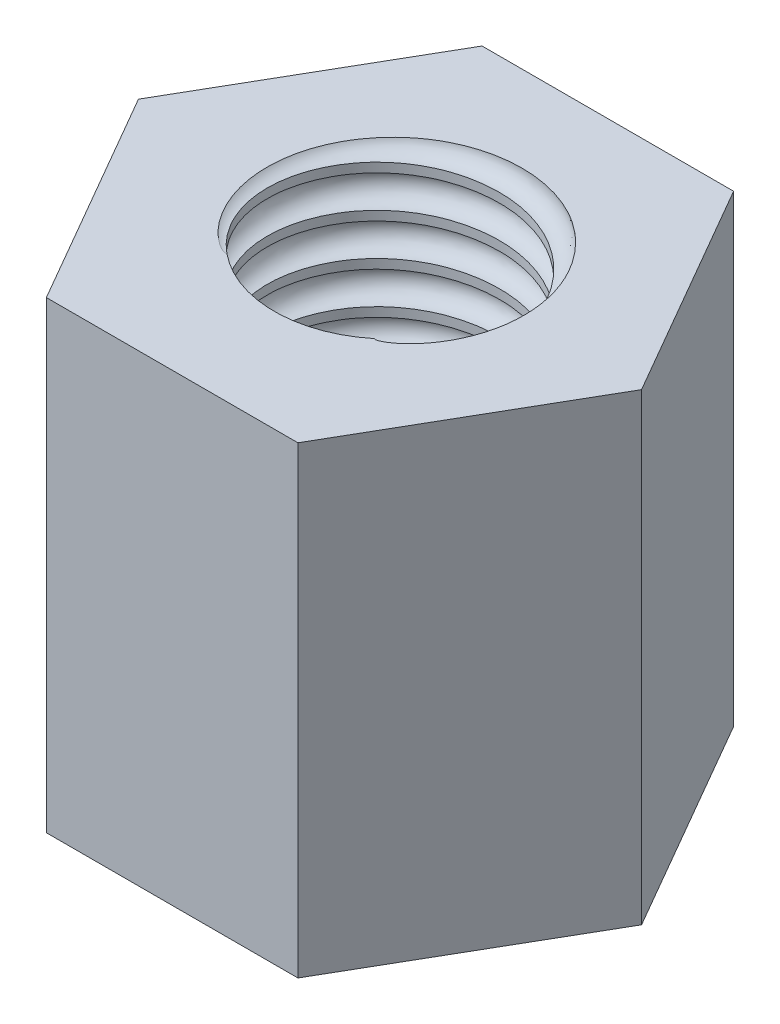
SolidWorks part; units mm, degrees
ref_plane "Front Plane" through (0, 0, 0) normal (0, 0, 1) x (1, 0, 0)
ref_plane "Top Plane" through (0, 0, 0) normal (0, 1, 0) x (1, 0, 0)
ref_plane "Right Plane" through (0, 0, 0) normal (1, 0, 0) x (0, 0, -1)
sketch "Sketch1" plane through (0, 0, 0) normal (0, 1, 0) x (1, 0, 0)
  line L1 (1.3568, -2.35) -> (2.7135, 0)
  line L2 (2.7135, 0) -> (1.3568, 2.35)
  line L3 (1.3568, 2.35) -> (-1.3568, 2.35)
  line L4 (-1.3568, 2.35) -> (-2.7135, 0)
  line L5 (-2.7135, 0) -> (-1.3568, -2.35)
  line L6 (-1.3568, -2.35) -> (1.3568, -2.35)
  circle A0 centre (0, 0) radius 2.35 construction
  point P1 (0, 2.35)
  dimension "D1" = 4.7
extrude "Boss-Extrude1" add sketch "Sketch1" along normal blind 5
sketch "Sketch2" plane through (0, 0, 0) normal (0, -1, 0) x (1, 0, 0)
  circle A0 centre (0, 0) radius 1.25
  dimension "D1" = 2.5
extrude "Boss-Extrude2" add sketch "Sketch2" along normal blind 6
sketch "Sketch4" plane through (0, -6, 0) normal (0, -1, 0) x (1, 0, 0)
  circle A0 centre (0, 0) radius 1.25 construction
  circle A1 centre (0, 0) radius 1.25
curve "Helix/Spiral1" pitch 0.45 height 5.9625 turns 13.25
sketch "Sketch5" plane through (0, 0, 0) normal (1, 0, 0) x (0, 0, -1)
  circle A0 centre (-1.25, -6) radius 0.15
  dimension "D1" = 0.3
sweep "Cut-Sweep3" cut profiles "Sketch5" path "Helix/Spiral1" align with end faces yes
sketch "Sketch9" plane through (0, 5, 0) normal (0, 1, 0) x (1, 0, 0)
  circle A0 centre (0, 0) radius 1.25
  dimension "D1" = 2.5
extrude "Cut-Extrude1" cut sketch "Sketch9" against normal blind 6
sketch "Sketch10" plane through (0, 5, 0) normal (0, 1, 0) x (1, 0, 0)
  circle A0 centre (0, 0) radius 1.25 construction
  circle A1 centre (0, 0) radius 1.25
curve "Helix/Spiral2" pitch 0.45 height 5.9625 turns 13.25
sketch "Sketch11" plane through (0, 0, 0) normal (1, 0, 0) x (0, 0, -1)
  circle A0 centre (1.25, 5) radius 0.175
  dimension "D1" = 0.35
sweep "Cut-Sweep4" cut profiles "Sketch11" path "Helix/Spiral2"
delete or keep bodies "Body-Delete/Keep 1" type delete bodies bodies 106
